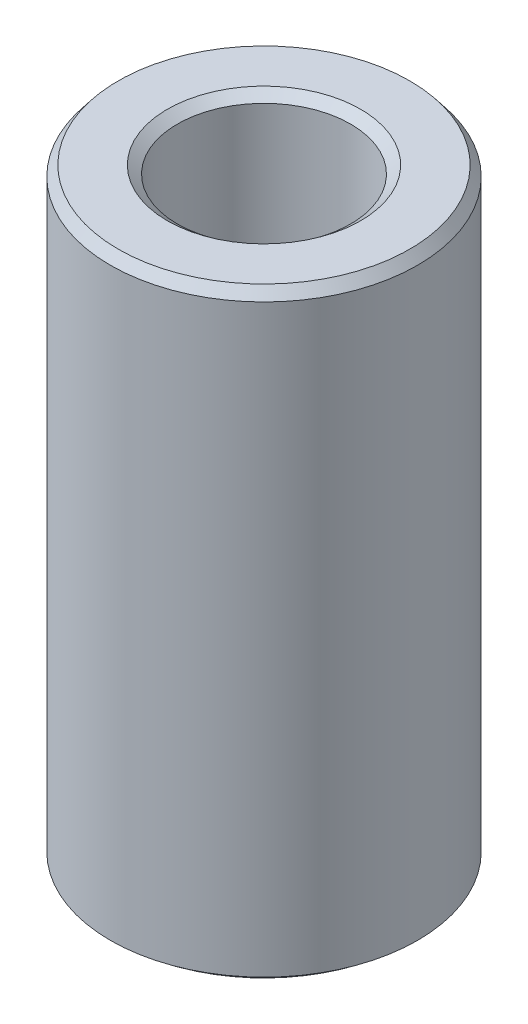
SolidWorks part; units mm, degrees
ref_plane "Front Plane" through (0, 0, 0) normal (0, 0, 1) x (1, 0, 0)
ref_plane "Top Plane" through (0, 0, 0) normal (0, 1, 0) x (1, 0, 0)
ref_plane "Right Plane" through (0, 0, 0) normal (1, 0, 0) x (0, 0, -1)
sketch "Sketch1" plane through (0, 0, 0) normal (0, 1, 0) x (1, 0, 0)
  circle A0 centre (0, 0) radius 55
  dimension "SLEEVE_OD" = 110
extrude "Boss-Extrude1" add sketch "Sketch1" along normal blind 215.766
sketch "Sketch2" plane through (0, 0, 0) normal (0, 1, 0) x (1, 0, 0)
  circle A0 centre (0, 0) radius 31.018
  dimension "BORE_D" = 62.0361
extrude "Cut-Extrude1" cut sketch "Sketch2" along normal through all
chamfer "Chamfer1" distance 3.5892 angle 37.959 4 edges at (0, 215.766, 31.018) (0, 0, 31.018) (0, 0, 55) (0, 215.766, 55) first distance on face at (0, 215.766, 31.018) first distance on face at (0, 0, 31.018) first distance on face at (0, 215.766, 55)
